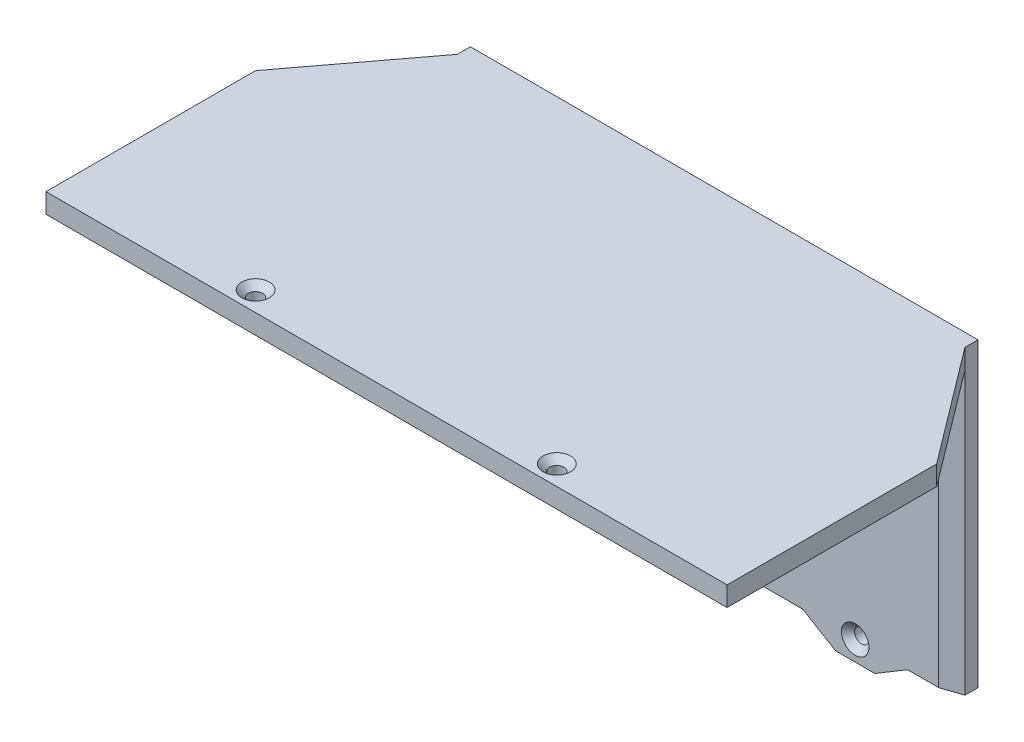
SolidWorks part; units mm, degrees
ref_plane "Płaszczyzna przednia" through (0, 0, 0) normal (0, 0, 1) x (1, 0, 0)
ref_plane "Płaszczyzna górna" through (0, 0, 0) normal (0, 1, 0) x (1, 0, 0)
ref_plane "Płaszczyzna prawa" through (0, 0, 0) normal (1, 0, 0) x (0, 0, -1)
sketch "Szkic1" plane through (0, 0, 0) normal (0, 1, 0) x (1, 0, 0)
  line L0 (-38.75, -24.1876) -> (38.75, -24.1876)
  line L1 (-38.75, -26.1829) -> (-52, -43.7453)
  line L2 (-52, -43.7453) -> (-52, -75.7453)
  line L3 (-60, -75.7453) -> (60, -75.7453)
  line L4 (38.75, -26.1829) -> (52, -43.7453)
  line L5 (52, -75.7453) -> (52, -43.7453)
  line L6 (38.75, 69.75) -> (38.75, -26.1829)
  line L7 (-38.75, 69.75) -> (38.75, 69.75)
  line L8 (-38.75, 69.75) -> (-38.75, -26.1829)
  line L9 (35.75, -27.1876) -> (38.75, -26.1829)
  line L10 (-35.75, -27.1876) -> (35.75, -27.1876)
  line L11 (-38.75, -26.1829) -> (-35.75, -27.1876)
  dimension "D1" = 120
  dimension "D2" = 32
  dimension "D3" = 22
  dimension "D4" = 22
  dimension "D5" = 3.1638
  dimension "D6" = 3.1638
  dimension "D7" = 95.9329
  dimension "D8" = 77.5
  dimension "D9" = 95.9329
  dimension "D10" = 1.9953
  dimension "D11" = 1.9953
  dimension "D12" = 104
extrude "Dodanie-wyciągnięcie1" add sketch "Szkic1" along normal blind 3 contours L11 L1 L2 L3 L5 L4 L9 L10 | L8 L11 L10 L9 L6 L0 region at (0, 0, 25.6723) region at (0, 0, 52.2478)
extrude "Dodanie-wyciągnięcie2" add sketch "Szkic1<3>" against normal blind 43 contours L8 L11 L10 L9 L6 L0 region at (0, 0, 25.6723)
sketch "Szkic1<3>" plane through (0, 0, 0) normal (0, 1, 0) x (1, 0, 0) same geometry as "Szkic1"
sketch "Szkic2" plane through (0, 0, 27.1876) normal (0, 0, 1) x (1, 0, 0)
  line L2 (26, -46) -> (20, -46)
  line L4 (-23, -40) -> (-23, -46) construction
  line L5 (-23, -43) -> (-23, -40) construction
  line L7 (-20, -40) -> (-26, -40)
  line L12 (26, -40) -> (26, -46)
  line L13 (20, -40) -> (20, -46)
  line L14 (23, -43) -> (23, -40) construction
  line L15 (23, -40) -> (23, -46) construction
  line L16 (0, -40) -> (0, -46) construction
  line L17 (-20, -43) -> (-24.1, -43)
  line L18 (20, -43) -> (24.1, -43)
  line L19 (20, -40) -> (26, -40)
  line L20 (-20, -40) -> (-20, -46)
  line L21 (-26, -40) -> (-26, -46)
  line L22 (-26, -46) -> (-20, -46)
  line L23 (35.75, -43) -> (35.75, 0) construction
  line L24 (-35.75, -43) -> (-35.75, 0) construction
  line L25 (-20, -46) -> (-15.0011, -43)
  line L26 (-35.75, -43) -> (35.75, -43) construction
  line L27 (-26, -46) -> (-30.9989, -43)
  line L28 (20, -46) -> (15.0011, -43)
  line L29 (26, -46) -> (30.9989, -43)
  circle A1 centre (23, -43) radius 1.1
  circle A2 centre (-23, -43) radius 1.1
  line M8 (-35.75, -43) -> (35.75, -43)
  dimension "D2" = 2.2
  dimension "D3" = 5.83
  dimension "D5" = 3
  dimension "D1" = 20
extrude "Dodanie-wyciągnięcie3" add sketch "Szkic2" against normal up to surface (3 mm away) contours L17 A2 L21 L22 L20 M8 | A2 M8 | A1 L13 L2 L12 M8 | L18 A1 | L27 L21 M8 | L20 L25 M8 | L28 L13 M8 | L12 L29 M8 region at (-18.3337, -44, 27.1876) region at (23, -44.622, 27.1876) region at (27.6663, -44, 27.1876) region at (18.3337, -44, 27.1876) region at (23, -43.4669, 27.1876) region at (-23, -44.622, 27.1876) region at (-27.6663, -44, 27.1876) region at (-23, -43.4669, 27.1876) up to face at (0, -20, 24.1876)
extrude "Wytnij-wyciągnięcie2" cut sketch "Szkic2<4>" against normal up to surface (3 mm away) contours A2 M8 | A2 M8 | L18 A1 | L18 A1 region at (23, -43.4669, 27.1876) region at (23, -42.5331, 27.1876) region at (-23, -43.4669, 27.1876) region at (-23, -42.5331, 27.1876) up to face at (0, -36.3333, 24.1876)
sketch "Szkic2<4>" plane through (0, 0, 27.1876) normal (0, 0, 1) x (1, 0, 0) same geometry as "Szkic2"
sketch "Szkic3" plane through (0, 3, 0) normal (0, 1, 0) x (1, 0, 0)
  line L1 (26, -75.7453) -> (20, -75.7453)
  line L2 (-23, -59.1535) -> (-23, -75.7453) construction
  line L3 (-23, -72.7453) -> (-23, -59.1535) construction
  line L4 (-20, -69.7453) -> (-26, -69.7453)
  line L5 (26, -69.7453) -> (26, -75.7453)
  line L6 (20, -69.7453) -> (20, -75.7453)
  line L7 (23, -72.7453) -> (23, -59.1535) construction
  line L8 (23, -59.1535) -> (23, -75.7453) construction
  line L9 (0, -59.1535) -> (0, -65.1535) construction
  line L11 (-52, -75.7453) -> (52, -75.7453) construction
  line L12 (20, -69.7453) -> (26, -69.7453)
  line L13 (-20, -69.7453) -> (-20, -75.7453)
  line L14 (-26, -69.7453) -> (-26, -75.7453)
  line L15 (-26, -75.7453) -> (-20, -75.7453)
  line L24 (-52, -43.7453) -> (-52, -75.7453) construction
  line L25 (52, -75.7453) -> (52, -43.7453) construction
  circle A2 centre (23, -72.7453) radius 1.1
  circle A3 centre (-23, -72.7453) radius 1.1
  point P10 (-26, -72.7453)
  dimension "D2" = 3
  dimension "D1" = 2.2
  dimension "D3" = 20
  dimension "D4" = 3
extrude "Wytnij-wyciągnięcie3" cut sketch "Szkic3" against normal up to surface (3 mm away) contours A3 | A2 region at (23, 3, 72.7453) region at (-23, 3, 72.7453) up to face at (0, 0, 43.2152)
chamfer "Sfazowanie1" distance 1 angle 45 1 edges at (-23, 3, 73.8453)
chamfer "Sfazowanie2" distance 1 angle 45 1 edges at (23, 3, 73.8453)
chamfer "Sfazowanie3" distance 1 angle 45 1 edges at (24.1, -43, 27.1876)
chamfer "Sfazowanie4" distance 1 angle 45 1 edges at (-21.9, -43, 27.1876)
